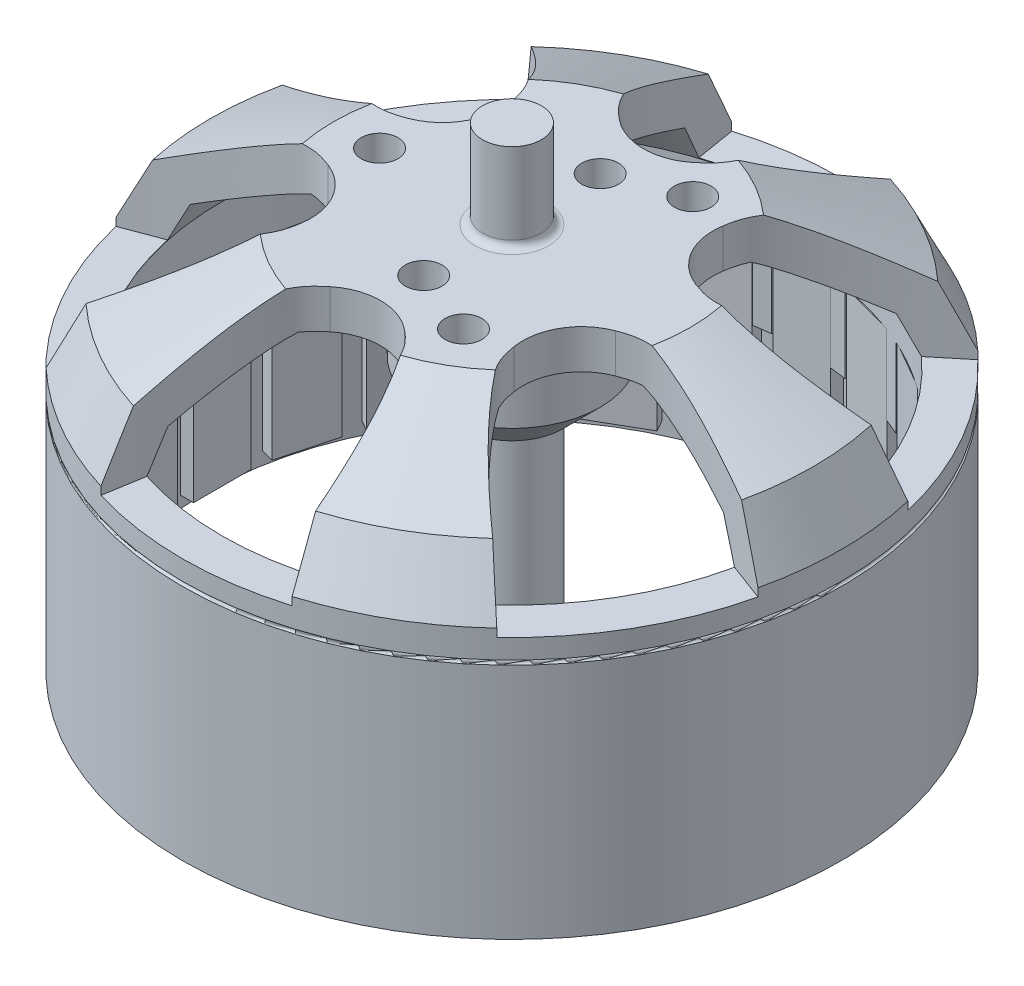
SolidWorks part; units mm, degrees
ref_plane "Front Plane" through (0, 0, 0) normal (0, 0, 1) x (1, 0, 0)
ref_plane "Top Plane" through (0, 0, 0) normal (0, 1, 0) x (1, 0, 0)
ref_plane "Right Plane" through (0, 0, 0) normal (1, 0, 0) x (0, 0, -1)
sketch "Sketch1" plane through (0, 0, 0) normal (0, 1, 0) x (1, 0, 0)
  circle A0 centre (0, 0) radius 22.41
  dimension "D1" = 44.82
extrude "Boss-Extrude1" add sketch "Sketch1" along normal mid plane 26.25
sketch "Sketch2" plane through (0, 0, 0) normal (0, 0, 1) x (1, 0, 0)
  line L0 (0, 0) -> (0, 13.125) construction
  line L1 (22.41, 13.125) -> (-22.41, 13.125) construction
  line L2 (22.41, -13.125) -> (22.41, 13.125) construction
  line L3 (12.125, 13.125) -> (20.5, 9.125)
  line L4 (20.5, 9.125) -> (22.41, 5.1993)
  line L5 (22.41, 5.1993) -> (24.1445, 16.7558)
  line L6 (24.1445, 16.7558) -> (12.125, 13.125)
  point P5 (12.125, 13.125)
  point P6 (20.5, 9.125)
  point P7 (22.41, 5.1993)
  dimension "D1" = 12.125
  dimension "D2" = 20.5
  dimension "D3" = 4
revolve "Cut-Revolve1" cut sketch "Sketch2" angle 360 about L0
sketch "Sketch3" plane through (0, 13.125, 0) normal (0, 1, 0) x (1, 0, 0)
  circle A0 centre (0, 0) radius 2
  dimension "D1" = 4
extrude "Boss-Extrude2" add sketch "Sketch3" along normal blind 6
shell "Shell3" thickness 2.66 removed face at (0, -13.125, 22.41)
sketch "Sketch9" plane through (0, 10.465, 0) normal (0, -1, 0) x (1, 0, 0)
  circle A0 centre (0, 0) radius 6
  dimension "D1" = 12
extrude "Boss-Extrude3" add sketch "Sketch9" along normal blind 7.6
sketch "Sketch10" plane through (0, 2.865, 0) normal (0, -1, 0) x (1, 0, 0)
  circle A0 centre (0, 0) radius 2.5
  dimension "D1" = 5
extrude "Boss-Extrude4" add sketch "Sketch10" along normal offset from surface (26.74 mm away) 43 up to face at (0, 19.125, 2)
chamfer "Chamfer1" distance 2.5 angle 45 1 edges at (0, 2.865, -6)
sketch "Sketch7" plane through (0, 13.125, 0) normal (0, 1, 0) x (1, 0, 0)
  line L0 (0, 0) -> (0, 22.41) construction
  circle A0 centre (0, 0) radius 22.41 construction
  arc A1 (-2.5231, 9.8312) -> (2.5231, 9.8312) centre (0, 12.935) ccw
  circle A2 centre (0, 0) radius 12.125 construction
  circle A3 centre (0, 0) radius 20.5 construction
  arc A4 (6.5, 21.4466) -> (-6.5, 21.4466) centre (0, 0) ccw
  arc A5 (21.8233, 5.0942) -> (15.3233, 16.3525) centre (0, 0) ccw
  arc A6 (7.2525, 7.1007) -> (9.7756, 2.7305) centre (11.202, 6.4675) ccw
  arc A7 (15.3233, -16.3525) -> (21.8233, -5.0942) centre (0, 0) ccw
  arc A8 (9.7756, -2.7305) -> (7.2525, -7.1007) centre (11.202, -6.4675) ccw
  arc A9 (-6.5, -21.4466) -> (6.5, -21.4466) centre (0, 0) ccw
  arc A10 (2.5231, -9.8312) -> (-2.5231, -9.8312) centre (0, -12.935) ccw
  arc A11 (-21.8233, -5.0942) -> (-15.3233, -16.3525) centre (0, 0) ccw
  arc A12 (-7.2525, -7.1007) -> (-9.7756, -2.7305) centre (-11.202, -6.4675) ccw
  arc A13 (-15.3233, 16.3525) -> (-21.8233, 5.0942) centre (0, 0) ccw
  arc A14 (-9.7756, 2.7305) -> (-7.2525, 7.1007) centre (-11.202, 6.4675) ccw
  spline S0 degree 3 poles (6.5, 21.4466) (5.8595, 17.1935) (5.0619, 13.9726) (3.634, 10.8813) (3.137, 10.3302) (2.5231, 9.8312) knots 0 0 0 0 0.635975 0.72893 0.929549 0.929549 0.929549 0.929549
  spline S1 degree 3 poles (-6.5, 21.4466) (-5.8595, 17.1935) (-5.0619, 13.9726) (-3.634, 10.8813) (-3.137, 10.3302) (-2.5231, 9.8312) knots 0 0 0 0 0.635975 0.72893 0.929549 0.929549 0.929549 0.929549
  spline S2 degree 3 poles (15.3233, 16.3525) (11.9602, 13.6712) (9.5697, 11.3701) (7.6065, 8.5878) (7.3777, 7.8819) (7.2525, 7.1007) knots 0 0 0 0 0.635975 0.72893 0.929549 0.929549 0.929549 0.929549
  spline S3 degree 3 poles (21.8233, 5.0942) (17.8197, 3.5223) (14.6316, 2.6026) (11.2405, 2.2935) (10.5147, 2.4484) (9.7756, 2.7305) knots 0 0 0 0 0.635975 0.72893 0.929549 0.929549 0.929549 0.929549
  spline S4 degree 3 poles (21.8233, -5.0942) (17.8197, -3.5223) (14.6316, -2.6026) (11.2405, -2.2935) (10.5147, -2.4484) (9.7756, -2.7305) knots 0 0 0 0 0.635975 0.72893 0.929549 0.929549 0.929549 0.929549
  spline S5 degree 3 poles (15.3233, -16.3525) (11.9602, -13.6712) (9.5697, -11.3701) (7.6065, -8.5878) (7.3777, -7.8819) (7.2525, -7.1007) knots 0 0 0 0 0.635975 0.72893 0.929549 0.929549 0.929549 0.929549
  spline S6 degree 3 poles (6.5, -21.4466) (5.8595, -17.1935) (5.0619, -13.9726) (3.634, -10.8813) (3.137, -10.3302) (2.5231, -9.8312) knots 0 0 0 0 0.635975 0.72893 0.929549 0.929549 0.929549 0.929549
  spline S7 degree 3 poles (-6.5, -21.4466) (-5.8595, -17.1935) (-5.0619, -13.9726) (-3.634, -10.8813) (-3.137, -10.3302) (-2.5231, -9.8312) knots 0 0 0 0 0.635975 0.72893 0.929549 0.929549 0.929549 0.929549
  spline S8 degree 3 poles (-15.3233, -16.3525) (-11.9602, -13.6712) (-9.5697, -11.3701) (-7.6065, -8.5878) (-7.3777, -7.8819) (-7.2525, -7.1007) knots 0 0 0 0 0.635975 0.72893 0.929549 0.929549 0.929549 0.929549
  spline S9 degree 3 poles (-21.8233, -5.0942) (-17.8197, -3.5223) (-14.6316, -2.6026) (-11.2405, -2.2935) (-10.5147, -2.4484) (-9.7756, -2.7305) knots 0 0 0 0 0.635975 0.72893 0.929549 0.929549 0.929549 0.929549
  spline S10 degree 3 poles (-21.8233, 5.0942) (-17.8197, 3.5223) (-14.6316, 2.6026) (-11.2405, 2.2935) (-10.5147, 2.4484) (-9.7756, 2.7305) knots 0 0 0 0 0.635975 0.72893 0.929549 0.929549 0.929549 0.929549
  spline S11 degree 3 poles (-15.3233, 16.3525) (-11.9602, 13.6712) (-9.5697, 11.3701) (-7.6065, 8.5878) (-7.3777, 7.8819) (-7.2525, 7.1007) knots 0 0 0 0 0.635975 0.72893 0.929549 0.929549 0.929549 0.929549
  point P7 (6.5, 21.4466)
  point P8 (3.9, 11.4807)
  point P13 (6.1, 19.5714)
  point P56 (0, 0)
  dimension "D1" = 8
  dimension "D2" = 6.5
  dimension "D3" = 3.9
  dimension "D4" = 12.935
  dimension "D5" = 6.1
  dimension "D6" = 6
extrude "Cut-Extrude3" cut sketch "Sketch7" against normal offset from surface (8.47 mm away) 17.78 up to face at (0, -13.125, 19.75)
sketch "Sketch8" plane through (0, 13.125, 0) normal (0, 1, 0) x (1, 0, 0)
  circle A3 centre (4.5, 7.7942) radius 1.25
  circle A4 centre (4.5, -7.7942) radius 1.25
  circle A5 centre (-9, 0) radius 1.25
  circle A6 centre (0, 6) radius 1.25
  circle A7 centre (0, -6) radius 1.25
  point P22 (0, 0)
extrude "Cut-Extrude4" cut sketch "Sketch8" against normal blind 17.78
fillet "Fillet2" radius 0.5 1 edges at (0, 13.125, 2)
sketch "Sketch11" plane through (0, 0, 0) normal (0, 0, 1) x (1, 0, 0)
  line L0 (-22.41, -13.125) -> (-22.41, 3.175) construction
  line L1 (-22.41, 5.1993) -> (-22.41, -13.125) construction
  line L2 (0, 0) -> (0, -23.875) construction
  line L3 (-2.5, -23.875) -> (2.5, -23.875) construction
  circle A0 centre (-22.41, 3.175) radius 0.15
  dimension "D2" = 0.3
  dimension "D1" = 16.3
revolve "Cut-Revolve3" cut sketch "Sketch11" angle 360 about L2
sketch "Sketch12" plane through (0, -13.125, 0) normal (0, -1, 0) x (-1, 0, 0)
  circle A0 centre (0, 0) radius 20.86
  circle A1 centre (0, 0) radius 19.75
  dimension "D1" = 41.72
extrude "Cut-Extrude5" cut sketch "Sketch12" against normal blind 9
sketch "Sketch13" plane through (0, -4.125, 0) normal (0, -1, 0) x (-1, 0, 0)
  line L0 (0, 0) -> (0, -19.75) construction
  line L1 (0, -19.75) -> (0, -20.8297) construction
  line L2 (2, -20.6485) -> (-2, -20.6485)
  line L3 (2, -20.6485) -> (2, -19.6485)
  line L4 (2, -19.6485) -> (-2, -19.6485)
  line L5 (-2, -20.6485) -> (-2, -19.6485)
  line L6 (2, -20.6485) -> (-2, -19.6485) construction
  line L7 (2, -19.6485) -> (-2, -20.6485) construction
  circle A0 centre (0, 0) radius 19.75 construction
  circle A1 centre (0, 0) radius 19.75 construction
  point P6 (0, -20.1485)
  dimension "D1" = 4
  dimension "D2" = 1
extrude "Cut-Extrude6" cut sketch "Sketch13" against normal offset from surface (5.36 mm away) 3.42 up to face at (-0.1117, 4.655, 20.5844)
pattern_circular "CirPattern1" count 24 over 360 about axis through (0, -73.9461, 0) along (0, 1, 0) of "Cut-Extrude6"
sketch "Sketch14" plane through (0, -4.125, 0) normal (0, -1, 0) x (1, 0, 0)
  line L0 (2, 19.6485) -> (-2, 20.6485) construction
  line L1 (-2, 20.6485) -> (-2, 19.6485) construction
  line L2 (-2, 19.6485) -> (2, 20.6485) construction
  line L3 (2, 20.6485) -> (2, 19.6485) construction
  line L5 (-2, 20.6485) -> (2, 20.6485) construction
  line L6 (2, 20.6485) -> (2, 19.6485) construction
  line L7 (2, 19.6485) -> (-2, 19.6485) construction
  line L8 (-2, 19.6485) -> (-2, 20.6485) construction
  line L9 (-1.95, 20.5985) -> (1.95, 20.5985)
  line L10 (1.95, 20.5985) -> (1.95, 19.6985)
  line L11 (1.95, 19.6985) -> (-1.95, 19.6985)
  line L12 (-1.95, 19.6985) -> (-1.95, 20.5985)
  dimension "D1" = 0.05
extrude "Boss-Extrude5" add sketch "Sketch14" against normal up to surface (5.36 mm away) and the other way offset from surface 1 up to face at (0, 1.235, 20.1739) other way up to face at (0, -13.125, -20.86)
pattern_circular "CirPattern2" count 24 every 15 about axis through (0, -73.9461, 0) along (0, 1, 0) of "Boss-Extrude5"
